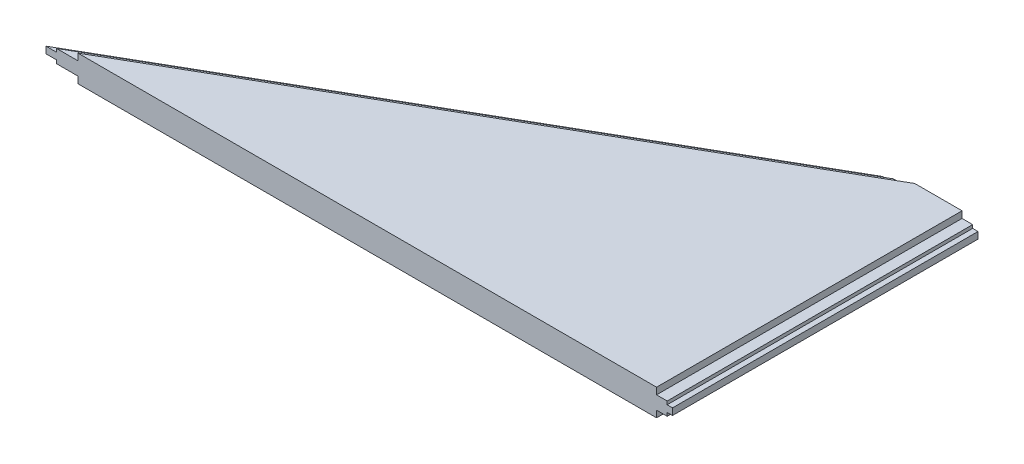
SolidWorks part; units mm, degrees
material "Dragonplate CF"
ref_plane "Front Plane" through (0, 0, 0) normal (0, 0, 1) x (1, 0, 0)
ref_plane "Top Plane" through (0, 0, 0) normal (0, 1, 0) x (1, 0, 0)
ref_plane "Right Plane" through (0, 0, 0) normal (1, 0, 0) x (0, 0, -1)
sketch "Sketch1" plane through (0, 0, 0) normal (0, 1, 0) x (1, 0, 0)
  line L0 (-406.4, 0) -> (0, 0)
  line L1 (0, 0) -> (0, 146.05)
  line L2 (0, 146.05) -> (-152.4, 146.05)
  line L3 (-152.4, 146.05) -> (-406.4, 0)
  dimension "D1" = 406.4
  dimension "D2" = 152.4
  dimension "D3" = 146.05
extrude "Boss-Extrude1" add sketch "Sketch1" along normal blind 6.35 and the other way blind 6.35 contours L3 L0 L1 L2
sketch "Sketch2" plane through (-100.9796, 0, -175.6167) normal (-0.4985, 0, -0.8669) x (-0.8669, 0, 0.4985)
  line L0 (59.3148, 6.35) -> (59.3148, 3.175)
  line L1 (59.3148, -6.35) -> (59.3148, 6.35) construction
  line L2 (59.3148, 3.175) -> (352.3107, 3.175)
  line L3 (352.3107, -6.35) -> (352.3107, 6.35) construction
  line L4 (352.3107, 3.175) -> (352.3107, 6.35)
  line L5 (352.3107, 6.35) -> (59.3148, 6.35)
  line L6 (59.3148, -6.35) -> (59.3148, -3.175)
  line L7 (59.3148, -6.35) -> (352.3107, -6.35)
  line L8 (352.3107, -6.35) -> (352.3107, -3.175)
  line L9 (352.3107, -3.175) -> (59.3148, -3.175)
  dimension "D1" = 3.175
  dimension "D2" = 3.175
extrude "Cut-Extrude1" cut sketch "Sketch2" against normal blind 38.1
sketch "Sketch3" plane through (0, 0, 0) normal (1, 0, 0) x (0, 0, -1)
  line L0 (0, 6.35) -> (0, 3.175)
  line L2 (0, 6.35) -> (146.05, 6.35)
  line L3 (146.05, 6.35) -> (146.05, 3.175)
  line L4 (146.05, -6.35) -> (146.05, 6.35) construction
  line L5 (0, 3.175) -> (146.05, 3.175)
  line L6 (0, -6.35) -> (0, -3.175)
  line L7 (0, -3.175) -> (146.05, -3.175)
  line L8 (146.05, -3.175) -> (146.05, -6.35)
  line L9 (146.05, -6.35) -> (0, -6.35)
  dimension "D1" = 3.175
  dimension "D2" = 3.175
  dimension "D3" = 3.175
  dimension "D4" = 3.175
extrude "Cut-Extrude2" cut sketch "Sketch3" against normal blind 38.1
sketch "Sketch4" plane through (0, 6.35, 0) normal (0, 1, 0) x (1, 0, 0)
  line L0 (-133.4083, 113.0209) -> (-75.9663, 146.05)
  line L1 (-38.1, 146.05) -> (-152.4, 146.05) construction
  line L2 (-75.9663, 146.05) -> (-152.4, 146.05)
  line L3 (-152.4, 146.05) -> (-133.4083, 113.0209)
  line L4 (-329.9663, 0) -> (-133.4083, 113.0209) construction
extrude "Cut-Extrude3" cut sketch "Sketch4" against normal blind 3.175
sketch "Sketch5" plane through (0, -6.35, 0) normal (0, -1, 0) x (1, 0, 0)
  line L0 (-133.4083, -113.0209) -> (-75.9663, -146.05)
  line L1 (-38.1, -146.05) -> (-152.4, -146.05) construction
  line L2 (-75.9663, -146.05) -> (-152.4, -146.05)
  line L3 (-152.4, -146.05) -> (-133.4083, -113.0209)
  line L4 (-329.9663, 0) -> (-133.4083, -113.0209) construction
extrude "Cut-Extrude4" cut sketch "Sketch5" against normal blind 3.175
sketch "Sketch6" plane through (0, 0, -146.05) normal (0, 0, -1) x (-1, 0, 0)
  line L0 (38.1, 6.35) -> (0, 0) construction
  line L1 (0, 0) -> (38.1, -6.35) construction
  line L2 (0, -3.175) -> (0, 3.175) construction
  line L3 (38.622, 3.2182) -> (19.3128, 0) construction
  line L4 (19.3128, 0) -> (38.622, -3.2182) construction
  line L5 (38.1, -3.175) -> (43.18, -3.175)
  line L6 (43.18, -3.175) -> (43.18, -6.35)
  line L7 (38.1, -6.35) -> (75.9663, -6.35) construction
  line L8 (43.18, -6.35) -> (38.1, -6.35)
  line L9 (38.1, 3.175) -> (43.18, 3.175)
  line L10 (43.18, 3.175) -> (43.18, 6.35)
  line L11 (38.1, 6.35) -> (75.9663, 6.35) construction
  line L12 (43.18, 6.35) -> (38.1, 6.35)
  line L13 (38.1, 6.35) -> (0, 6.35)
  line L14 (0, 6.35) -> (0, -6.35)
  line L15 (0, -6.35) -> (38.1, -6.35)
  line L16 (38.1, -3.175) -> (38.1, -1.5875)
  line L22 (38.1, -1.5875) -> (35.56, -1.5875)
  line L23 (35.56, -1.5875) -> (35.56, 1.5875)
  line L24 (35.56, 1.5875) -> (38.1, 1.5875)
  line L25 (38.1, 1.5875) -> (38.1, 3.175)
  line M7 (75.9663, 6.35) -> (38.1, 6.35)
  line M8 (38.1, 6.35) -> (38.1, 3.175)
  line M9 (38.1, 3.175) -> (0, 3.175)
  line M10 (0, 3.175) -> (0, -3.175)
  line M11 (0, -3.175) -> (38.1, -3.175)
  line M12 (38.1, -3.175) -> (38.1, -6.35)
  line M13 (38.1, -6.35) -> (75.9663, -6.35)
  dimension "D2" = 1.5875
  dimension "D1" = 3.175
  dimension "D3" = 5.08
  dimension "D4" = 5.08
  dimension "D5" = 2.54
  dimension "D6" = 3.175
extrude "Cut-Extrude5" cut sketch "Sketch6" against normal blind 157.099 contours L9 L10 M7 M8 | L6 L5 M12 M13 | L4 L3 M11 M9 M10 | L4 L3 region at (-18.4369, 0, -146.05) region at (-40.64, -4.7625, -146.05) region at (-40.64, 4.7625, -146.05)
sketch "Sketch7" plane through (0, -3.175, 0) normal (0, -1, 0) x (1, 0, 0)
  line L0 (-152.4, -146.05) -> (-133.4083, -113.0209) construction
  line L1 (-329.9663, 0) -> (-75.9663, -146.05) construction
  line L2 (-75.9663, -146.05) -> (-329.9663, 0) construction
ref_plane "Plane1" through (-51.4204, 0, 29.5667) normal (-0.8669, 0, 0.4985) x (0.4985, 0, 0.8669)
sketch "Sketch8" plane through (-51.4204, 0, 29.5667) normal (-0.8669, 0, 0.4985) x (0.4985, 0, 0.8669)
  line L0 (-202.5787, 0) -> (-164.4787, 0) construction
  line L1 (-202.5787, -3.175) -> (-202.5787, 3.175) construction
  line L2 (-164.4787, 0) -> (-164.4787, -6.35) construction
  line L3 (-164.4787, -6.35) -> (-202.5787, 0) construction
  line L4 (-202.5787, 0) -> (-164.4787, 6.35) construction
  line L5 (-164.4787, 0) -> (-164.4787, 6.35) construction
  line L6 (-163.9567, -3.2182) -> (-183.2659, 0) construction
  line L7 (-183.2659, 0) -> (-163.9567, 3.2182) construction
  line L8 (-164.4787, 3.175) -> (-159.3987, 3.175)
  line L9 (-159.3987, 3.175) -> (-159.3987, 6.35)
  line L10 (-159.3987, 6.35) -> (-164.4787, 6.35)
  line L11 (-164.4787, -3.175) -> (-159.3987, -3.175)
  line L12 (-159.3987, -3.175) -> (-159.3987, -6.35)
  line L13 (-159.3987, -6.35) -> (-164.4787, -6.35)
  line L14 (-164.4787, 6.35) -> (-202.5787, 6.35)
  line L15 (-202.5787, 6.35) -> (-202.5787, -6.35)
  line L16 (-202.5787, -6.35) -> (-164.4787, -6.35)
  line L17 (-164.4787, -3.175) -> (-164.4787, -1.5875)
  line L23 (-164.4787, -1.5875) -> (-167.0187, -1.5875)
  line L24 (-167.0187, -1.5875) -> (-167.0187, 1.5875)
  line L25 (-167.0187, 1.5875) -> (-164.4787, 1.5875)
  line L26 (-164.4787, 1.5875) -> (-164.4787, 3.175)
  point P7 (-164.4787, -3.175)
  point P11 (-164.4787, 3.175)
  dimension "D5" = 1.5875
  dimension "D1" = 38.1
  dimension "D2" = 6.35
  dimension "D3" = 6.35
  dimension "D6" = 5.08
  dimension "D7" = 3.175
  dimension "D8" = 5.08
  dimension "D9" = 3.175
  dimension "D10" = 38.1
  dimension "D11" = 12.7
  dimension "D12" = 3.175
  dimension "D13" = 2.54
  dimension "D4" = 3.175
extrude "Cut-Extrude6" cut sketch "Sketch8" against normal blind 157.099 and the other way blind 339.217 contours L8 L9 L10 L14 L15 L16 L13 L12 L11 L6 L7 | L7 L6 region at (-142.3615, 0, -128.5917)
